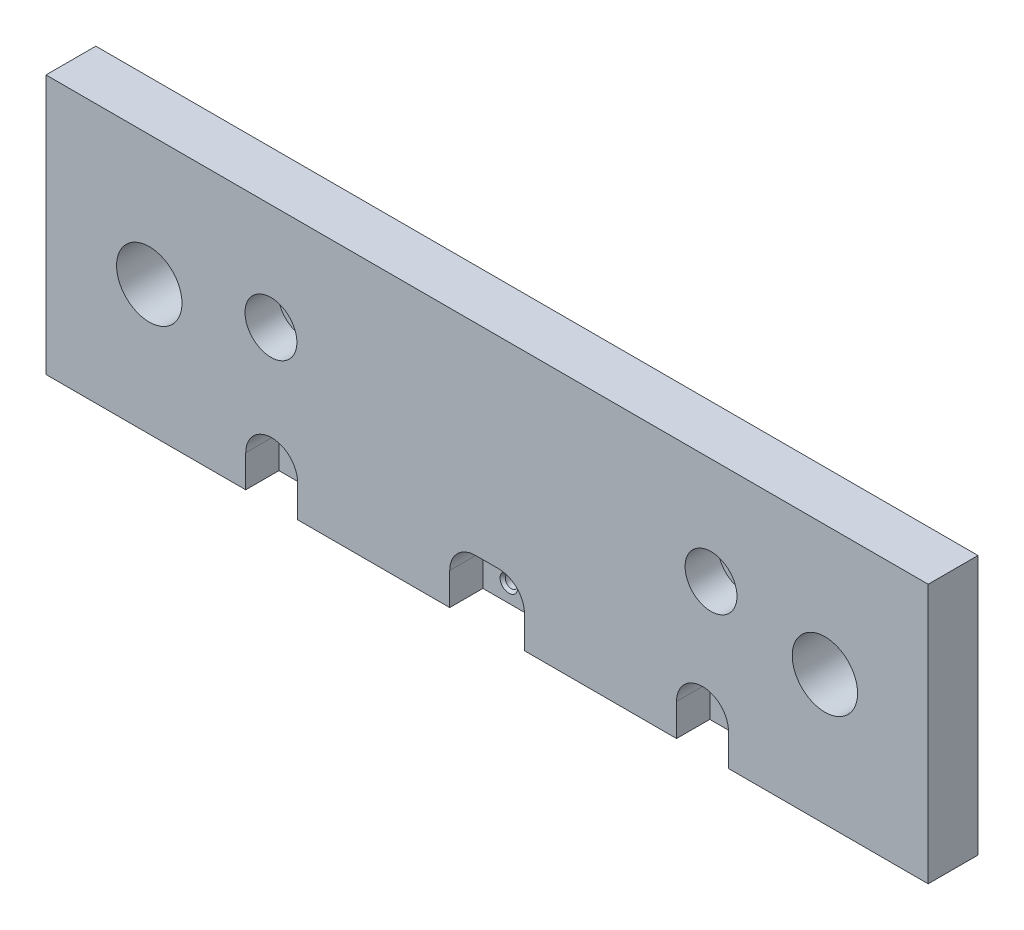
SolidWorks part; units mm, degrees
ref_plane "Front Plane" through (0, 0, 0) normal (0, 0, 1) x (1, 0, 0)
ref_plane "Top Plane" through (0, 0, 0) normal (0, 1, 0) x (1, 0, 0)
ref_plane "Right Plane" through (0, 0, 0) normal (1, 0, 0) x (0, 0, -1)
sketch "Sketch1" plane through (0, 0, 0) normal (0, 0, 1) x (1, 0, 0)
  line L1 (-42.5, 12.5) -> (42.5, 12.5)
  line L2 (-42.5, 12.5) -> (-42.5, -12.5)
  line L3 (-42.5, -12.5) -> (42.5, -12.5)
  line L4 (42.5, 12.5) -> (42.5, -12.5)
  line L5 (-42.5, 12.5) -> (42.5, -12.5) construction
  line L6 (-42.5, -12.5) -> (42.5, 12.5) construction
  point P0 (0, 0)
  dimension "D1" = 25
  dimension "D2" = 85
extrude "Boss-Extrude1" add sketch "Sketch1" along normal blind 6.3
sketch "Sketch2" plane through (0, 0, 6.3) normal (0, 0, 1) x (1, 0, 0)
  line L0 (42.5, -12.5) -> (42.5, 12.5) construction
  line L1 (-42.5, 12.5) -> (-42.5, -12.5) construction
  circle A0 centre (32.55, 0) radius 3.15
  circle A1 centre (-32.55, 0) radius 3.15
  dimension "D1" = 6.3
  dimension "D2" = 6.3
  dimension "D3" = 9.95
  dimension "D4" = 9.95
extrude "Cut-Extrude1" cut sketch "Sketch2" against normal through all
sketch "Sketch3" plane through (0, 0, 0) normal (0, 0, -1) x (-1, 0, 0)
  line L0 (-45.4395, -14.9211) -> (-45.4395, 15.1916)
  line L1 (-22.5, 8.7) -> (22.5, 8.7)
  line L2 (-22.5, 8.7) -> (-22.5, -8.7)
  line L3 (-22.5, -8.7) -> (22.5, -8.7)
  line L4 (22.5, 8.7) -> (22.5, -8.7)
  line L5 (-22.5, 8.7) -> (22.5, -8.7) construction
  line L6 (-22.5, -8.7) -> (22.5, 8.7) construction
  line L7 (-45.4395, 15.1916) -> (44.7183, 15.1916)
  line L8 (44.7183, 15.1916) -> (44.7183, -15.9128)
  line L9 (44.7183, -15.9128) -> (-45.4395, -14.9211)
  circle A2 centre (-32.55, 0) radius 4.95
  circle A3 centre (-32.55, 0) radius 4.95
  circle A5 centre (32.55, 0) radius 4.95
  circle A6 centre (32.55, 0) radius 4.95
  point P0 (0, 0)
  dimension "D3" = 45
  dimension "D4" = 17.4
  dimension "D1" = 1.8
  dimension "D2" = 1.8
extrude "Cut-Extrude3" cut sketch "Sketch3" against normal blind 1.5
sketch "Sketch4" plane through (0, 0, 6.3) normal (0, 0, 1) x (1, 0, 0)
  line L0 (-32.8174, -10.8) -> (33.1781, -10.8) construction
  line L1 (-42.5, -12.5) -> (42.5, -12.5) construction
  line L2 (0, -12.5) -> (0, 12.5) construction
  line L3 (42.5, 12.5) -> (-42.5, 12.5) construction
  line L4 (-32.8174, -9.4) -> (33.1781, -9.4) construction
  circle A0 centre (-1.1, -10.8) radius 0.6
  circle A1 centre (1.1, -10.8) radius 0.6
  circle A2 centre (-20.755, -10.8) radius 0.6
  circle A3 centre (20.755, -10.8) radius 0.6
  circle A4 centre (-1.1, -9.4) radius 0.6
  circle A5 centre (1.1, -9.4) radius 0.6
  circle A6 centre (20.755, -9.4) radius 0.6
  circle A7 centre (-20.755, -9.4) radius 0.6
  dimension "D2" = 1.2
  dimension "D3" = 1.2
  dimension "D6" = 1.2
  dimension "D7" = 1.2
  dimension "D11" = 1.2
  dimension "D12" = 1.2
  dimension "D13" = 1.2
  dimension "D14" = 1.2
  dimension "D1" = 1.7
  dimension "D4" = 1.1
  dimension "D5" = 1.1
  dimension "D8" = 20.755
  dimension "D9" = 20.755
  dimension "D10" = 1.4
  dimension "D15" = 20.755
  dimension "D16" = 20.755
extrude "Cut-Extrude4" cut sketch "Sketch4" against normal through all
sketch "Sketch6" plane through (0, 0, 6.3) normal (0, 0, 1) x (1, 0, 0)
  circle A0 centre (-20.825, 2.27) radius 0.6
  circle A1 centre (21.575, 2.27) radius 0.6
  circle A2 centre (-20.755, -9.4) radius 0.6 construction
  circle A3 centre (20.755, -9.4) radius 0.6 construction
  dimension "D1" = 1.2
  dimension "D2" = 1.2
  dimension "D3" = 11.67
  dimension "D4" = 11.67
  dimension "D5" = 21.575
  dimension "D6" = 20.825
extrude "Cut-Extrude5" cut sketch "Sketch6" against normal through all
sketch "Sketch7" plane through (0, 0, 6.3) normal (0, 0, 1) x (1, 0, 0)
sketch "Sketch8" plane through (0, 0, 6.3) normal (0, 0, 1) x (1, 0, 0)
  line L0 (18.255, -12.5) -> (23.255, -12.5)
  line L2 (18.255, -9.4) -> (18.255, -12.5)
  line L3 (23.255, -9.4) -> (23.255, -12.5)
  line L4 (-1.1, -6.9) -> (1.1, -6.9)
  line L6 (-23.255, -12.5) -> (-18.255, -12.5)
  line L7 (-3.6, -12.5) -> (3.6, -12.5)
  line L8 (-23.255, -9.4) -> (-23.255, -12.5)
  line L9 (-18.255, -9.4) -> (-18.255, -12.5)
  line L10 (-3.6, -9.4) -> (-3.6, -12.5)
  line L11 (3.6, -9.4) -> (3.6, -12.5)
  arc A0 (23.255, -9.4) -> (18.255, -9.4) centre (20.755, -9.4) ccw
  arc A1 (-18.255, -9.4) -> (-23.255, -9.4) centre (-20.755, -9.4) ccw
  arc A4 (-1.1, -6.9) -> (-3.6, -9.4) centre (-1.1, -9.4) ccw
  arc A5 (3.6, -9.4) -> (1.1, -6.9) centre (1.1, -9.4) ccw
  circle A6 centre (-20.825, 2.27) radius 2.5
  circle A7 centre (21.575, 2.27) radius 2.5
  dimension "D1" = 5
  dimension "D2" = 5
extrude "Cut-Extrude6" cut sketch "Sketch8" against normal blind 3.2
chamfer "Chamfer1" distance 0.25 angle 45 10 edges at (-20.225, 2.27, 3.1) (22.175, 2.27, 3.1) (21.355, -10.8, 3.1) (21.355, -9.4, 3.1) (1.7, -10.8, 3.1) (1.7, -9.4, 3.1) (-0.5, -10.8, 3.1) (-0.5, -9.4, 3.1) (-20.155, -10.8, 3.1) (-20.155, -9.4, 3.1)
